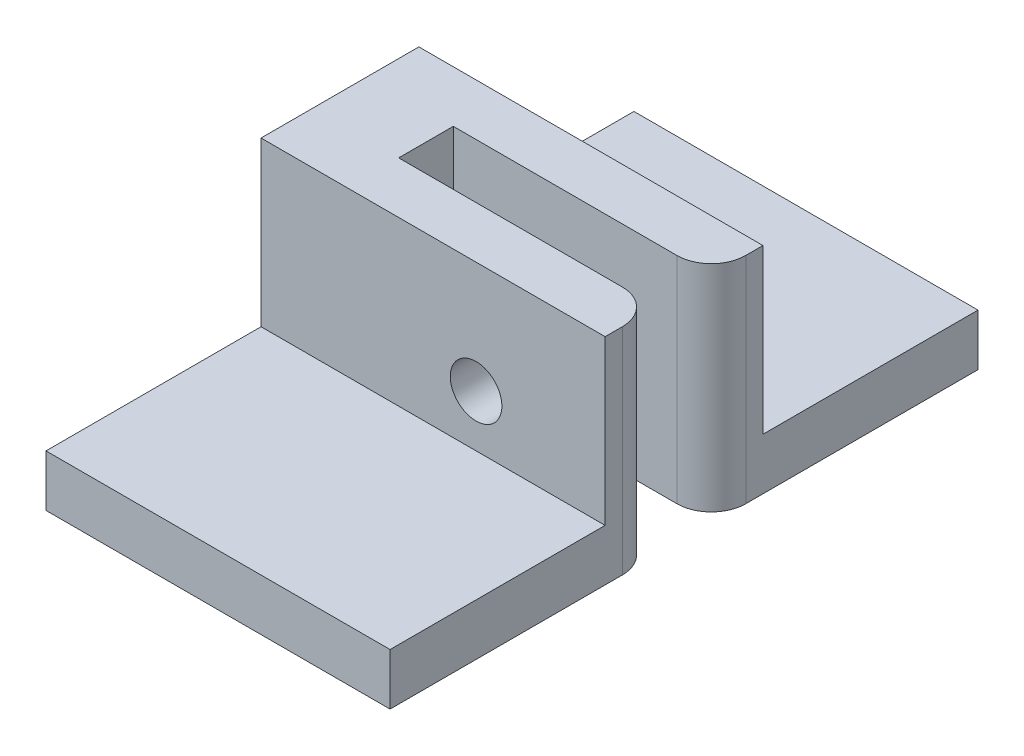
SolidWorks part; units mm, degrees
ref_plane "Front Plane" through (0, 0, 0) normal (0, 0, 1) x (1, 0, 0)
ref_plane "Top Plane" through (0, 0, 0) normal (0, 1, 0) x (1, 0, 0)
ref_plane "Right Plane" through (0, 0, 0) normal (1, 0, 0) x (0, 0, -1)
sketch "Sketch1" plane through (0, 0, 0) normal (1, 0, 0) x (0, 0, -1)
  line L0 (0, 12.5) -> (3, 12.5)
  line L1 (0, 0) -> (-3.175, 0)
  line L2 (0, 0) -> (0, 12.5) construction
  line L3 (0, 12.5) -> (-3.175, 12.5)
  line L4 (-3.175, 0) -> (-3.175, 12.5) construction
  line L5 (3, 12.5) -> (3, 3)
  line L6 (3, 3) -> (15.5, 3)
  line L7 (15.5, 3) -> (15.5, 0)
  line L8 (15.5, 0) -> (0, 0)
  line L9 (-1.5875, 12.5) -> (-1.5875, 0) construction
  line L10 (-18.675, 0) -> (-3.175, 0)
  line L11 (-18.675, 3) -> (-18.675, 0)
  line L12 (-6.175, 3) -> (-18.675, 3)
  line L13 (-6.175, 12.5) -> (-6.175, 3)
  line L14 (-3.175, 12.5) -> (-6.175, 12.5)
  dimension "D1" = 3.175
  dimension "D2" = 12.5
  dimension "D3" = 3
  dimension "D4" = 3
  dimension "D5" = 12.5
extrude "Boss-Extrude1" add sketch "Sketch1" along normal blind 20
sketch "Sketch2" plane through (20, 0, 0) normal (1, 0, 0) x (0, 0, -1)
  line L0 (-1.5875, 12.5) -> (-1.5875, 0) construction
  line L1 (3, 12.5) -> (-6.175, 12.5) construction
  line L2 (-18.675, 0) -> (15.5, 0) construction
  line L4 (-3.175, 12.5) -> (0, 12.5)
  line L5 (-3.175, 12.5) -> (-3.175, 0)
  line L6 (-3.175, 0) -> (0, 0)
  line L7 (0, 12.5) -> (0, 0)
  line L8 (-3.175, 12.5) -> (0, 0) construction
  line L9 (-3.175, 0) -> (0, 12.5) construction
  point P6 (-1.5875, 6.25)
extrude "Cut-Extrude1" cut sketch "Sketch2" against normal blind 15
sketch "Sketch3" plane through (0, 0, 6.175) normal (0, 0, 1) x (1, 0, 0)
  line L0 (5, 12.5) -> (5, 3) construction
  line L1 (20, 12.5) -> (0, 12.5) construction
  line L2 (20, 3) -> (0, 3) construction
  line L3 (0, 12.5) -> (0, 3) construction
  line L4 (5, 6) -> (20, 6) construction
  line L5 (20, 12.5) -> (20, 3) construction
  line L6 (20, 0) -> (0, 0) construction
  circle A0 centre (12.5, 6) radius 1.5
  dimension "D2" = 3
  dimension "D1" = 5
  dimension "D3" = 6
extrude "Cut-Extrude2" cut sketch "Sketch3" against normal through all
fillet "Fillet1" radius 2 2 edges at (20, 6.25, 3.175) (20, 6.25, 0)
scale "Scale1" scale about centroid uniform scaling yes scale factor 1.02
